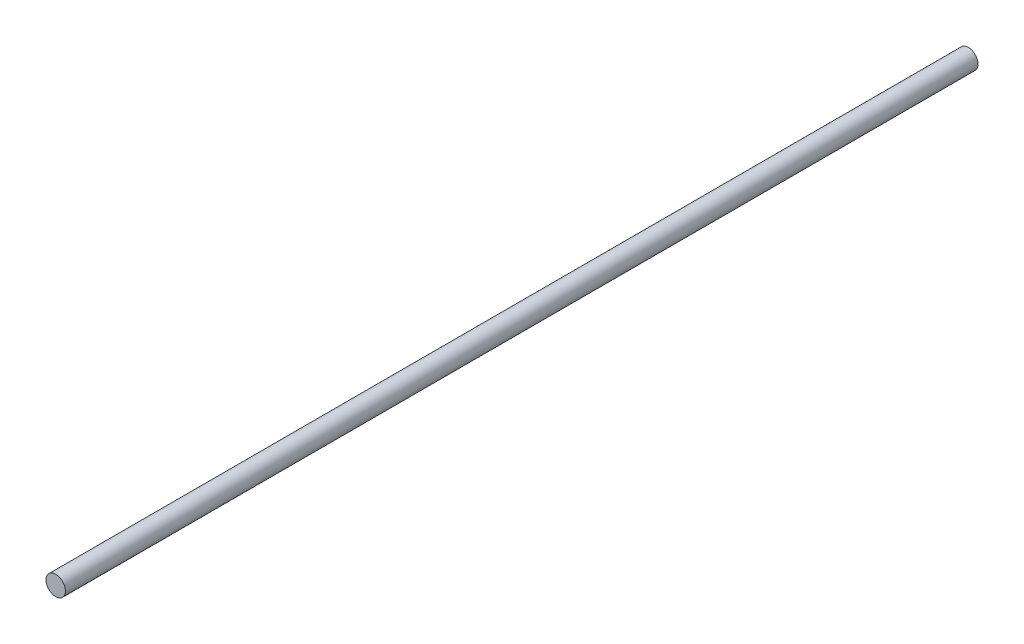
SolidWorks part; units mm, degrees
ref_plane "Front Plane" through (0, 0, 0) normal (0, 0, 1) x (1, 0, 0)
ref_plane "Top Plane" through (0, 0, 0) normal (0, 1, 0) x (1, 0, 0)
ref_plane "Right Plane" through (0, 0, 0) normal (1, 0, 0) x (0, 0, -1)
sketch "Sketch1" plane through (0, 0, 0) normal (0, 0, 1) x (1, 0, 0)
  line L5 (-1.7678, 1.7678) -> (1.7678, -1.7678) construction
  line L6 (-1.7678, -1.7678) -> (1.7678, 1.7678) construction
  circle A0 centre (0, 0) radius 2.5
  point P0 (0, 0)
  dimension "D3" = 5
extrude "Boss-Extrude1" add sketch "Sketch1" along normal mid plane 235
sketch "Sketch2" plane through (0, 0, 117.5) normal (0, 0, 1) x (1, 0, 0)
  circle A0 centre (0, 0) radius 4.7826
